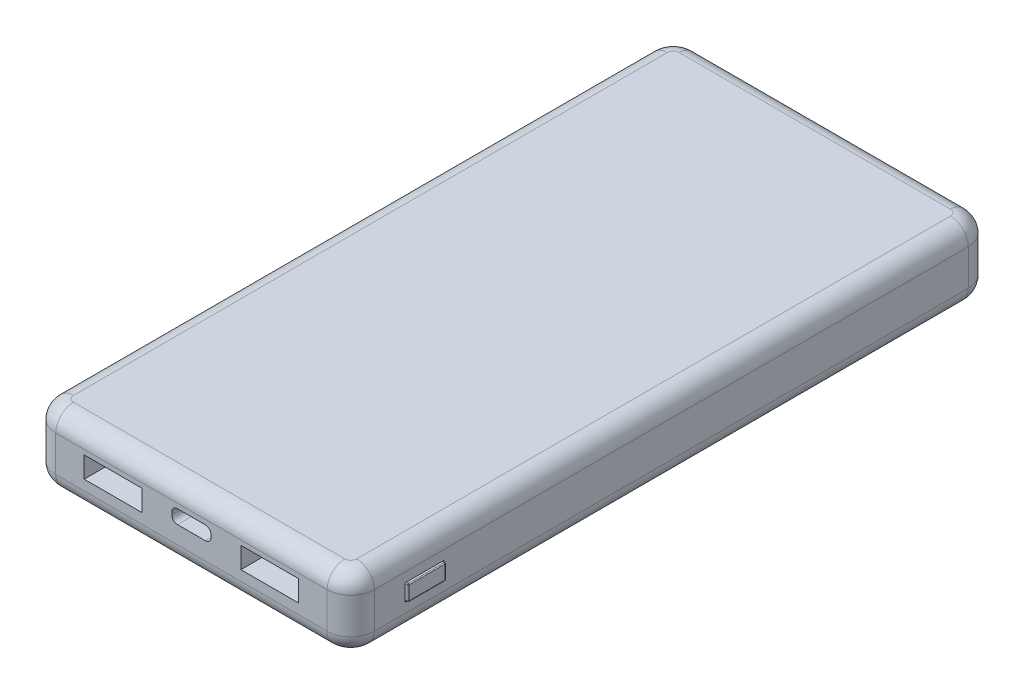
SolidWorks part; units mm, degrees
ref_plane "Front Plane" through (0, 0, 0) normal (0, 0, 1) x (1, 0, 0)
ref_plane "Top Plane" through (0, 0, 0) normal (0, 1, 0) x (1, 0, 0)
ref_plane "Right Plane" through (0, 0, 0) normal (1, 0, 0) x (0, 0, -1)
sketch "Sketch1" plane through (0, 0, 0) normal (0, 1, 0) x (1, 0, 0)
  line L0 (0, 0) -> (67.3, 0)
  line L1 (67.3, 0) -> (67.3, 135.4)
  line L2 (67.3, 135.4) -> (0, 135.4)
  line L3 (0, 135.4) -> (0, 0)
  dimension "D1" = 135.4
  dimension "D2" = 67.3
extrude "Boss-Extrude1" add sketch "Sketch1" along normal blind 15.1
fillet "Fillet1" radius 5 4 edges at (0, 7.55, -135.4) (67.3, 7.55, -135.4) (67.3, 7.55, 0) (0, 7.55, 0)
fillet "Fillet2" radius 3.75 8 edges at (1.4645, 15.1, -1.4645) (0, 15.1, -67.7) (1.4645, 15.1, -133.9355) (33.65, 15.1, -135.4) (65.8355, 15.1, -133.9355) (67.3, 15.1, -67.7) (65.8355, 15.1, -1.4645) (33.65, 15.1, 0)
sketch "Sketch2" plane through (0, 0, 0) normal (0, 0, 1) x (1, 0, 0)
  line L0 (11, 5.9) -> (11, 10.35)
  line L1 (11, 10.35) -> (23.2, 10.35)
  line L2 (23.2, 10.35) -> (23.2, 5.9)
  line L3 (23.2, 5.9) -> (11, 5.9)
  line L4 (33.65, 0) -> (33.65, 18.9371) construction
  line L5 (5, 0) -> (62.3, 0) construction
  line L7 (56.3, 5.9) -> (56.3, 10.35)
  line L8 (44.1, 10.35) -> (44.1, 5.9)
  line L9 (56.3, 10.35) -> (44.1, 10.35)
  line L10 (44.1, 5.9) -> (56.3, 5.9)
  line L11 (30.7, 7.45) -> (36.6, 7.45)
  line L12 (29.5, 8.65) -> (29.5, 9.15)
  line L13 (30.7, 10.35) -> (36.6, 10.35)
  line L14 (37.8, 9.15) -> (37.8, 8.65)
  line L15 (62.3, 11.35) -> (5, 11.35) construction
  arc A0 (36.6, 10.35) -> (37.8, 9.15) centre (36.6, 9.15) cw
  arc A1 (37.8, 8.65) -> (36.6, 7.45) centre (36.6, 8.65) cw
  arc A2 (30.7, 10.35) -> (29.5, 9.15) centre (30.7, 9.15) ccw
  arc A3 (30.7, 7.45) -> (29.5, 8.65) centre (30.7, 8.65) cw
  point P18 (33.65, 7.45)
  point P23 (37.8, 7.45)
  point P26 (29.5, 10.35)
  point P29 (29.5, 7.45)
  dimension "D8" = 1.2
  dimension "D1" = 1
  dimension "D3" = 12.2
  dimension "D4" = 4.45
  dimension "D5" = 8.3
  dimension "D6" = 1
  dimension "D7" = 2.9
  dimension "D9" = 10.45
extrude "Cut-Extrude1" cut sketch "Sketch2" against normal blind 6
sketch "Sketch3" plane through (67.3, 0, 0) normal (1, 0, 0) x (0, 0, -1)
  line L1 (11.5, 5.85) -> (19.7, 5.85)
  line L2 (11.5, 5.85) -> (11.5, 9.35)
  line L3 (11.5, 9.35) -> (19.7, 9.35)
  line L4 (19.7, 5.85) -> (19.7, 9.35)
  line L5 (11.6, 5.95) -> (19.6, 5.95)
  line L6 (11.6, 5.95) -> (11.6, 9.25)
  line L7 (11.6, 9.25) -> (19.6, 9.25)
  line L8 (19.6, 5.95) -> (19.6, 9.25)
  line L9 (130.4, 11.35) -> (5, 11.35) construction
  line L10 (0, 0) -> (0, 11.35) construction
  dimension "D1" = 11.5
  dimension "D2" = 0.1
  dimension "D3" = 0.1
  dimension "D4" = 8.2
  dimension "D5" = 3.5
  dimension "D6" = 2
  dimension "D7" = 0.1
  dimension "D8" = 0.1
extrude "Cut-Extrude2" cut sketch "Sketch3" against normal blind 3
fillet "Fillet3" radius 3.75 8 edges at (1.4645, 0, -1.4645) (0, 0, -67.7) (1.4645, 0, -133.9355) (33.65, 0, -135.4) (65.8355, 0, -133.9355) (67.3, 0, -67.7) (65.8355, 0, -1.4645) (33.65, 0, 0)
sketch "Sketch4" plane through (67.3, 0, 0) normal (1, 0, 0) x (0, 0, -1)
  line L0 (11.6, 9.25) -> (19.6, 9.25)
  line L1 (19.6, 9.25) -> (19.6, 5.95)
  line L2 (19.6, 5.95) -> (11.6, 5.95)
  line L3 (11.6, 5.95) -> (11.6, 9.25)
extrude "Boss-Extrude2" add sketch "Sketch4" along normal blind 0.5
fillet "Fillet4" radius 0.2 4 edges at (66.05, 5.95, -11.6) (66.05, 5.95, -19.6) (66.05, 9.25, -19.6) (66.05, 9.25, -11.6)
fillet "Fillet5" radius 0.2 8 edges at (67.8, 9.1914, -19.5414) (67.8, 7.6, -19.6) (67.8, 6.0086, -19.5414) (67.8, 5.95, -15.6) (67.8, 6.0086, -11.6586) (67.8, 7.6, -11.6) (67.8, 9.1914, -11.6586) (67.8, 9.25, -15.6)
ref_plane "Plane1" through (33.65, 0, 0) normal (1, 0, 0) x (0, 0, -1)
ref_plane "Plane2" through (0, 0, 0) normal (0, 0, 1) x (1, 0, 0)
ref_axis "Axis1" through (33.65, 7.45, 0) along (0, 1, 0)
ref_plane "Plane3" through (0, 8.9, 0) normal (0, 1, 0) x (1, 0, 0)
ref_axis "Axis2" through (37.8, 8.9, 0) along (-1, 0, 0)
ref_point "Point1"
sketch "Sketch5" plane through (0, 0, -6) normal (0, 0, 1) x (1, 0, 0)
  line L0 (29.5, 8.9) -> (37.8, 8.9) construction
  line L1 (30.74, 8.35) -> (36.56, 8.35)
  line L2 (30.2, 8.89) -> (30.2, 8.91)
  line L3 (30.74, 9.45) -> (36.56, 9.45)
  line L4 (37.1, 8.89) -> (37.1, 8.91)
  line L5 (29.5, 9.15) -> (29.5, 8.65) construction
  line L6 (37.8, 8.65) -> (37.8, 9.15) construction
  line L7 (30.2, 9.45) -> (37.1, 8.35) construction
  line L8 (30.2, 8.35) -> (37.1, 9.45) construction
  arc A0 (36.56, 9.45) -> (37.1, 8.91) centre (36.56, 8.91) cw
  arc A1 (37.1, 8.89) -> (36.56, 8.35) centre (36.56, 8.89) cw
  arc A2 (30.74, 8.35) -> (30.2, 8.89) centre (30.74, 8.89) cw
  arc A3 (30.2, 8.91) -> (30.74, 9.45) centre (30.74, 8.91) cw
  point P10 (33.65, 8.9)
  point P11 (33.65, 8.9)
  dimension "D3" = 0.54
  dimension "D1" = 6.9
  dimension "D2" = 1.1
extrude "Boss-Extrude3" add sketch "Sketch5" along normal blind 2.1
